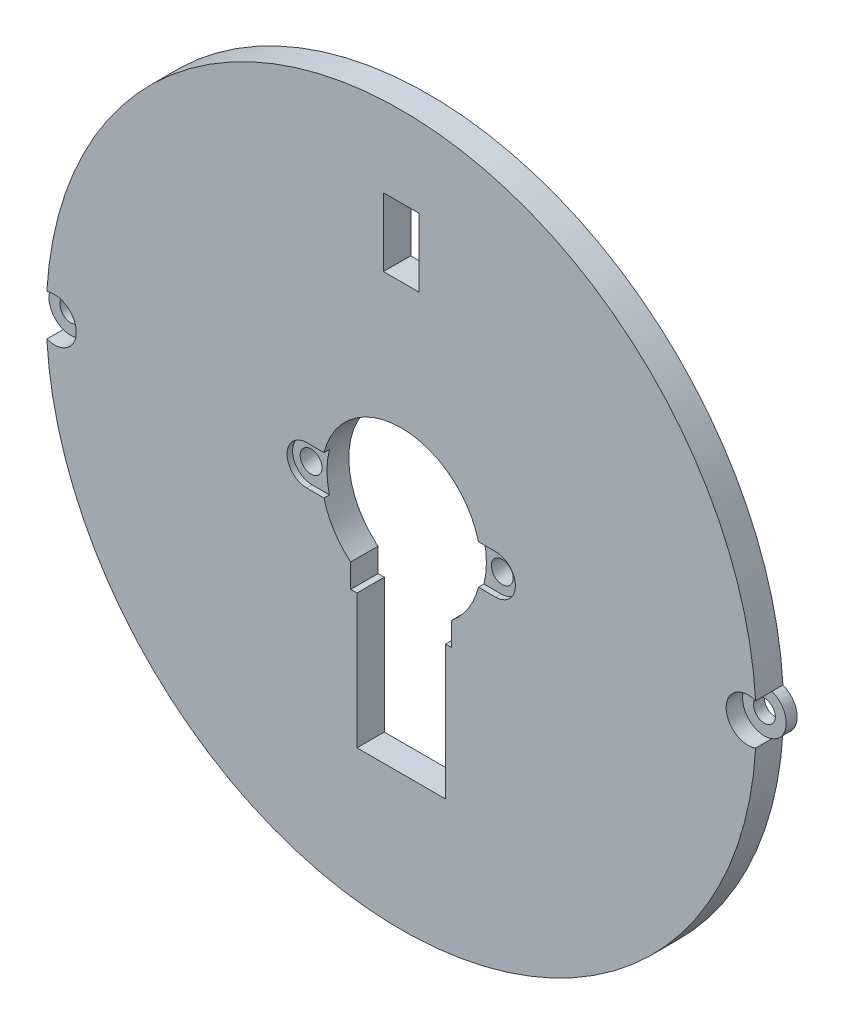
SolidWorks part; units mm, degrees
ref_plane "Front Plane" through (0, 0, 0) normal (0, 0, 1) x (1, 0, 0)
ref_plane "Top Plane" through (0, 0, 0) normal (0, 1, 0) x (1, 0, 0)
ref_plane "Right Plane" through (0, 0, 0) normal (1, 0, 0) x (0, 0, -1)
sketch "Sketch1" plane through (0, 0, 0) normal (0, 0, 1) x (1, 0, 0)
  line L0 (-121.4648, 0) -> (89.658, 0) construction
  line L1 (0, 59.7877) -> (0, -65.1952) construction
  line L2 (-14.1492, 3.6) -> (-17.3, 3.6)
  line L3 (-14.1492, -3.6) -> (-17.3, -3.6)
  line L4 (-9.25, -11.2959) -> (-9.25, -15.647)
  line L5 (14.1492, 3.6) -> (17.3, 3.6)
  line L14 (8.1, -15.647) -> (8.1, -40.2)
  line L15 (14.1492, -3.6) -> (17.3, -3.6)
  line L16 (-8.1, -40.2) -> (8.1, -40.2)
  line L24 (9.25, -11.2959) -> (9.25, -15.647)
  line L25 (8.1, -15.647) -> (9.25, -15.647)
  line L26 (-8.1, -15.647) -> (-9.25, -15.647)
  line L27 (-8.1, -15.647) -> (-8.1, -40.2)
  line L28 (-3.25, 44) -> (3.25, 44) construction
  line L29 (-3.25, 50.25) -> (3.25, 50.25)
  line L30 (-3.25, 50.25) -> (-3.25, 37.75)
  line L31 (-3.25, 37.75) -> (3.25, 37.75)
  line L32 (3.25, 50.25) -> (3.25, 37.75)
  circle A0 centre (0, 0) radius 65
  arc A2 (9.25, -11.2959) -> (-9.25, -11.2959) centre (0, 0) ccw
  arc A3 (17.3, -3.6) -> (17.3, 3.6) centre (17.3, 0) ccw
  arc A4 (-17.3, -3.6) -> (-17.3, 3.6) centre (-17.3, 0) cw
  circle A6 centre (17.5, 0) radius 2
  circle A7 centre (-17.5, 0) radius 2
  circle A8 centre (0, 56) radius 2
  circle A9 centre (0, 32) radius 2
  circle A10 centre (63.5, 0) radius 4
  circle A11 centre (63.5, 0) radius 2
  circle A12 centre (-63.5, 0) radius 4
  circle A13 centre (-63.5, 0) radius 2
  point P35 (0, -40.2)
  dimension "D2" = 18.5
  dimension "D3" = 14.6
  dimension "D4" = 7.2
  dimension "D8" = 4
  dimension "D17" = 8
  dimension "D5" = 130
  dimension "D13" = 4
  dimension "D18" = 4
  dimension "D6" = 1.15
  dimension "D7" = 0.2
  dimension "D9" = 6.5
  dimension "D10" = 4.3511
  dimension "D11" = 12.5
  dimension "D12" = 44
  dimension "D14" = 40.2
  dimension "D15" = 12
  dimension "D16" = 17.5
  dimension "D19" = 63.5
extrude "Boss-Extrude1" add sketch "Sketch1" along normal blind 5 contours A0 L3 A4 L2 A2 L5 A3 L15 L24 L25 L14 L16 L27 L26 L4 region at (57.6631, 0, 0)
extrude "Boss-Extrude2" add sketch "Sketch1<3>" along normal blind 4 contours A4 L3 A2 L2 A7 | L15 A3 L5 A2 A6 region at (-14.6987, 0, 0) region at (15.7246, 3.5013, 0)
sketch "Sketch1<3>" plane through (0, 0, 0) normal (0, 0, 1) x (1, 0, 0) same geometry as "Sketch1"
extrude "Boss-Extrude3" add sketch "Sketch1<4>" along normal blind 1 contours A7 | A6 region at (17.5, 0, 0) region at (-17.5, 0, 0)
sketch "Sketch1<4>" plane through (0, 0, 0) normal (0, 0, 1) x (1, 0, 0) same geometry as "Sketch1"
extrude "Boss-Extrude6" add sketch "Sketch1<6>" along normal blind 5 contours A8 | A9 region at (0, 56, 0) region at (0, 32, 0)
sketch "Sketch1<6>" plane through (0, 0, 0) normal (0, 0, 1) x (1, 0, 0) same geometry as "Sketch1"
extrude "Cut-Extrude1" cut sketch "Sketch1<7>" along normal blind 3 contours A9 | A8 region at (0, 56, 0) region at (0, 32, 0)
sketch "Sketch1<7>" plane through (0, 0, 0) normal (0, 0, 1) x (1, 0, 0) same geometry as "Sketch1"
extrude "Boss-Extrude7" add sketch "Sketch1<8>" along normal blind 2 contours A0 A13 A12 | A0 A13 A12 | A11 A0 A10 | A11 A0 A10 region at (61.403, 0, 0) region at (66.0706, 0, 0) region at (-61.2714, 3.2042, 0) region at (-66.0706, 0, 0)
sketch "Sketch1<8>" plane through (0, 0, 0) normal (0, 0, 1) x (1, 0, 0) same geometry as "Sketch1"
